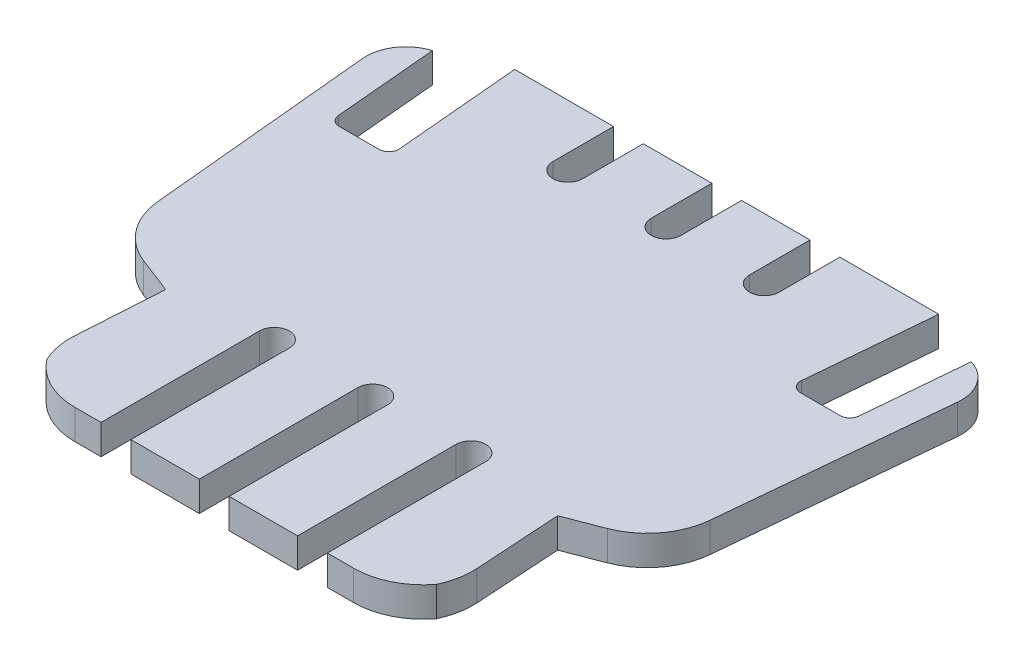
SolidWorks part; units mm, degrees
ref_plane "Front Plane" through (0, 0, 0) normal (0, 0, 1) x (1, 0, 0)
ref_plane "Top Plane" through (0, 0, 0) normal (0, 1, 0) x (1, 0, 0)
ref_plane "Right Plane" through (0, 0, 0) normal (1, 0, 0) x (0, 0, -1)
sketch "Sketch1" plane through (0, 0, 0) normal (0, 1, 0) x (1, 0, 0)
  line L0 (-1.5, 6.1) -> (-1.5, 0)
  line L1 (1.5, 0) -> (1.5, 6.1)
  line L2 (1.5, 6.1) -> (8.39, 6.1)
  line L3 (8.39, 6.1) -> (8.39, 0)
  line L4 (11.39, 0) -> (11.39, 6.1)
  line L5 (11.39, 6.1) -> (21.345, 6.1)
  line L6 (21.345, 6.1) -> (20.1212, -7.7)
  line L7 (20.1212, -7.7) -> (26.1212, -7.7)
  line L8 (26.1212, -7.7) -> (27.1233, 3.6)
  line L9 (27.1233, 3.6) -> (30.3533, 3.6)
  line L10 (30.3533, 3.6) -> (27.375, -27.7)
  line L11 (27.375, -27.7) -> (19.725, -30.65)
  line L12 (19.725, -30.65) -> (20.405, -41.49)
  line L13 (20.405, -41.49) -> (17.97, -45.49)
  line L14 (17.97, -45.49) -> (11.39, -45.49)
  line L15 (11.39, -45.49) -> (11.39, -29.54)
  line L16 (8.39, -29.54) -> (8.39, -45.49)
  line L17 (8.39, -45.49) -> (1.5, -45.49)
  line L18 (1.5, -45.49) -> (1.5, -29.54)
  line L19 (-1.5, -29.54) -> (-1.5, -45.49)
  line L20 (0, -55) -> (0, 55) construction
  line L21 (-8.39, -45.49) -> (-1.5, -45.49)
  line L22 (-8.39, -29.54) -> (-8.39, -45.49)
  line L23 (-11.39, -45.49) -> (-11.39, -29.54)
  line L24 (-17.97, -45.49) -> (-11.39, -45.49)
  line L25 (-20.405, -41.49) -> (-17.97, -45.49)
  line L26 (-19.725, -30.65) -> (-20.405, -41.49)
  line L27 (-27.375, -27.7) -> (-19.725, -30.65)
  line L28 (-30.3533, 3.6) -> (-27.375, -27.7)
  line L29 (-27.1233, 3.6) -> (-30.3533, 3.6)
  line L30 (-26.1212, -7.7) -> (-27.1233, 3.6)
  line L31 (-20.1212, -7.7) -> (-26.1212, -7.7)
  line L32 (-21.345, 6.1) -> (-20.1212, -7.7)
  line L33 (-11.39, 6.1) -> (-21.345, 6.1)
  line L34 (-11.39, 0) -> (-11.39, 6.1)
  line L35 (-8.39, 6.1) -> (-8.39, 0)
  line L36 (-1.5, 6.1) -> (-8.39, 6.1)
  arc A0 (-1.5, 0) -> (1.5, 0) centre (0, 0) ccw
  arc A1 (8.39, 0) -> (11.39, 0) centre (9.89, 0) ccw
  arc A2 (11.39, -29.54) -> (8.39, -29.54) centre (9.89, -29.54) ccw
  arc A3 (1.5, -29.54) -> (-1.5, -29.54) centre (0, -29.54) ccw
  arc A4 (-11.39, -29.54) -> (-8.39, -29.54) centre (-9.89, -29.54) cw
  arc A5 (-8.39, 0) -> (-11.39, 0) centre (-9.89, 0) cw
  point P30 (0, -28.04)
  point P36 (9.89, -1.5)
  dimension "D1" = 1.5
  dimension "D18" = 7.6
  dimension "D2" = 13.8
  dimension "D3" = 17.45
  dimension "D4" = 16.78
  dimension "D5" = 42.69
  dimension "D6" = 6
  dimension "D7" = 2.5
  dimension "D8" = 3.23
  dimension "D9" = 31.3
  dimension "D10" = 19.725
  dimension "D11" = 20.405
  dimension "D12" = 51.59
  dimension "D13" = 4
  dimension "D14" = 14.84
  dimension "D15" = 27.375
  dimension "D16" = 35.94
  dimension "D17" = 84.932
extrude "Boss-Extrude1" add sketch "Sketch1" along normal blind 3
fillet "Fillet1" radius 4 2 edges at (-30.3533, 1.5, -3.6) (30.3533, 1.5, -3.6)
fillet "Fillet2" radius 1 4 edges at (26.1212, 1.5, 7.7) (20.1212, 1.5, 7.7) (-20.1212, 1.5, 7.7) (-26.1212, 1.5, 7.7)
fillet "Fillet3" radius 7 6 edges at (-17.97, 1.5, 45.49) (17.97, 1.5, 45.49) (-20.405, 1.5, 41.49) (20.405, 1.5, 41.49) (-27.375, 1.5, 27.7) (27.375, 1.5, 27.7)
